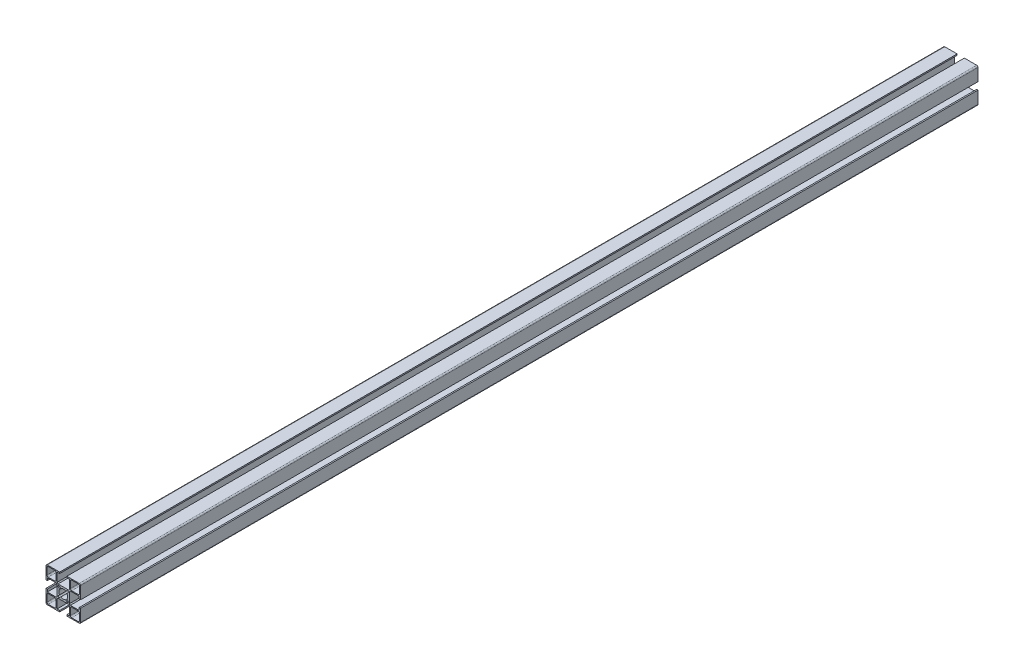
SolidWorks part; units mm, degrees
note: '?' marks a value the reader was unsure of.
material "6063-T5"
ref_plane "前视基准面" through (0, 0, 0) normal (0, 0, 1) x (1, 0, 0)
ref_plane "上视基准面" through (0, 0, 0) normal (0, 1, 0) x (1, 0, 0)
ref_plane "右视基准面" through (0, 0, 0) normal (1, 0, 0) x (0, 0, -1)
sketch "草图1" plane through (0, 0, 0) normal (0, 0, 1) x (1, 0, 0)
  line L0 (-6.0893, -7.15) -> (6.0893, -7.15)
  line L1 (7.15, -8.2107) -> (6.0893, -7.15)
  line L2 (-7.15, -8.2107) -> (-6.0893, -7.15)
  line L3 (7.15, -8.2107) -> (7.15, -18.5)
  line L4 (-7.15, -8.2107) -> (-7.15, -18.5)
  line L5 (4.2, -18.5) -> (7.15, -18.5)
  line L6 (-4.2, -18.5) -> (-7.15, -18.5)
  line L7 (4.2, -18.5) -> (4.2, -20)
  line L8 (-4.2, -18.5) -> (-4.2, -20)
  line L9 (4.2, -20) -> (18.5, -20)
  line L10 (-4.2, -20) -> (-18.5, -20)
  line L11 (20, -18.5) -> (20, -4.2)
  line L12 (-20, -18.5) -> (-20, -4.2)
  line L13 (20, -4.2) -> (18.5, -4.2)
  line L14 (-20, -4.2) -> (-18.5, -4.2)
  line L15 (18.5, -4.2) -> (18.5, -7.15)
  line L16 (-18.5, -4.2) -> (-18.5, -7.15)
  line L17 (18.5, -7.15) -> (8.2107, -7.15)
  line L18 (-18.5, -7.15) -> (-8.2107, -7.15)
  line L19 (8.2107, -7.15) -> (7.15, -6.0893)
  line L20 (-8.2107, -7.15) -> (-7.15, -6.0893)
  line L21 (7.15, 6.0893) -> (7.15, -6.0893)
  line L22 (-7.15, 6.0893) -> (-7.15, -6.0893)
  line L23 (8.2107, 7.15) -> (7.15, 6.0893)
  line L24 (-8.2107, 7.15) -> (-7.15, 6.0893)
  line L25 (18.5, 7.15) -> (8.2107, 7.15)
  line L26 (-18.5, 7.15) -> (-8.2107, 7.15)
  line L27 (18.5, 4.2) -> (18.5, 7.15)
  line L28 (-18.5, 4.2) -> (-18.5, 7.15)
  line L29 (20, 4.2) -> (18.5, 4.2)
  line L30 (-20, 4.2) -> (-18.5, 4.2)
  line L31 (20, 18.5) -> (20, 4.2)
  line L32 (-20, 18.5) -> (-20, 4.2)
  line L33 (4.2, 20) -> (18.5, 20)
  line L34 (-4.2, 20) -> (-18.5, 20)
  line L35 (4.2, 18.5) -> (4.2, 20)
  line L36 (-4.2, 18.5) -> (-4.2, 20)
  line L37 (4.2, 18.5) -> (7.15, 18.5)
  line L38 (-4.2, 18.5) -> (-7.15, 18.5)
  line L39 (7.15, 8.2107) -> (7.15, 18.5)
  line L40 (-7.15, 8.2107) -> (-7.15, 18.5)
  line L41 (7.15, 8.2107) -> (6.0893, 7.15)
  line L42 (-7.15, 8.2107) -> (-6.0893, 7.15)
  line L43 (6.0893, 7.15) -> (-6.0893, 7.15)
  line L44 (17.4, 8.25) -> (9.75, 8.25)
  line L45 (8.25, 9.75) -> (8.25, 17.4)
  line L46 (18.9, 17.4) -> (18.9, 9.75)
  line L47 (9.75, 18.9) -> (17.4, 18.9)
  line L48 (-8.25, 17.4) -> (-8.25, 9.75)
  line L49 (-17.4, 18.9) -> (-9.75, 18.9)
  line L50 (-9.75, 8.25) -> (-17.4, 8.25)
  line L51 (-18.9, 9.75) -> (-18.9, 17.4)
  line L52 (-17.4, -8.25) -> (-9.75, -8.25)
  line L53 (-8.25, -9.75) -> (-8.25, -17.4)
  line L54 (-18.9, -17.4) -> (-18.9, -9.75)
  line L55 (-9.75, -18.9) -> (-17.4, -18.9)
  line L56 (8.25, -17.4) -> (8.25, -9.75)
  line L57 (17.4, -18.9) -> (9.75, -18.9)
  line L58 (9.75, -8.25) -> (17.4, -8.25)
  line L59 (18.9, -9.75) -> (18.9, -17.4)
  line L60 (-4.2433, 2.8291) -> (-5.6569, 4.2426)
  line L61 (-5.6569, -4.2426) -> (-4.2433, -2.8291)
  line L62 (-4.2426, 5.6569) -> (-2.8291, 4.2433)
  line L63 (-2.8291, -4.2433) -> (-4.2426, -5.6569)
  line L64 (2.8291, 4.2433) -> (4.2426, 5.6569)
  line L65 (4.2426, -5.6569) -> (2.8291, -4.2433)
  line L66 (5.6569, 4.2426) -> (4.2433, 2.8291)
  line L67 (4.2433, -2.8291) -> (5.6569, -4.2426)
  arc A0 (18.5, -20) -> (20, -18.5) centre (18.5, -18.5) ccw
  arc A1 (-20, -18.5) -> (-18.5, -20) centre (-18.5, -18.5) ccw
  arc A2 (20, 18.5) -> (18.5, 20) centre (18.5, 18.5) ccw
  arc A3 (-18.5, 20) -> (-20, 18.5) centre (-18.5, 18.5) ccw
  arc A4 (8.25, 9.75) -> (9.75, 8.25) centre (9.75, 9.75) ccw
  arc A5 (17.4, 8.25) -> (18.9, 9.75) centre (17.4, 9.75) ccw
  arc A6 (9.75, 18.9) -> (8.25, 17.4) centre (9.75, 17.4) ccw
  arc A7 (18.9, 17.4) -> (17.4, 18.9) centre (17.4, 17.4) ccw
  arc A8 (-8.25, 17.4) -> (-9.75, 18.9) centre (-9.75, 17.4) ccw
  arc A9 (-9.75, 8.25) -> (-8.25, 9.75) centre (-9.75, 9.75) ccw
  arc A10 (-17.4, 18.9) -> (-18.9, 17.4) centre (-17.4, 17.4) ccw
  arc A11 (-18.9, 9.75) -> (-17.4, 8.25) centre (-17.4, 9.75) ccw
  arc A12 (-8.25, -9.75) -> (-9.75, -8.25) centre (-9.75, -9.75) ccw
  arc A13 (-17.4, -8.25) -> (-18.9, -9.75) centre (-17.4, -9.75) ccw
  arc A14 (-9.75, -18.9) -> (-8.25, -17.4) centre (-9.75, -17.4) ccw
  arc A15 (-18.9, -17.4) -> (-17.4, -18.9) centre (-17.4, -17.4) ccw
  arc A16 (8.25, -17.4) -> (9.75, -18.9) centre (9.75, -17.4) ccw
  arc A17 (9.75, -8.25) -> (8.25, -9.75) centre (9.75, -9.75) ccw
  arc A18 (17.4, -18.9) -> (18.9, -17.4) centre (17.4, -17.4) ccw
  arc A19 (18.9, -9.75) -> (17.4, -8.25) centre (17.4, -9.75) ccw
  arc A20 (-4.2433, 2.8291) -> (-4.2433, -2.8291) centre (0, 0) ccw
  arc A21 (-4.2426, 5.6569) -> (-5.6569, 4.2426) centre (-4.9497, 4.9497) ccw
  arc A22 (-5.6569, -4.2426) -> (-4.2426, -5.6569) centre (-4.9497, -4.9497) ccw
  arc A23 (2.8291, 4.2433) -> (-2.8291, 4.2433) centre (0, 0) ccw
  arc A24 (-2.8291, -4.2433) -> (2.8291, -4.2433) centre (0, 0) ccw
  arc A25 (5.6569, 4.2426) -> (4.2426, 5.6569) centre (4.9497, 4.9497) ccw
  arc A26 (4.2426, -5.6569) -> (5.6569, -4.2426) centre (4.9497, -4.9497) ccw
  arc A27 (4.2433, -2.8291) -> (4.2433, 2.8291) centre (0, 0) ccw
extrude "凸台-拉伸1" add sketch "草图1" along normal blind 1040
ref_axis "基准轴" through (0, 0, 0) along (0, 0, 1)?
ref_plane "基准面" through (0, 0, 20) normal (0, 0, -1) x (-1, 0, 0)
hole_wizard "螺纹孔E" [suppressed] positions "草图3" profile "草图2" tap size "M12" standard "GB"
sketch "草图3" plane through (0, 0, 300) normal (0, 0, 1) x (1, 0, 0)
  point P0 (0, 0)
sketch "草图2" plane through (0, 0, 300) normal (1, 0, 0) x (0, -1, 0)
  line L0 (0, 0) -> (0, 31.8174)
  line L1 (0, 31.8174) -> (5.105, 28.75)
  line L2 (5.105, 28.75) -> (5.105, 0)
  line L5 (5.105, 0) -> (0, 0)
  line L10 (0, 31.8174) -> (-5.105, 28.75) construction
  line L11 (0, -6.35) -> (0, 107.95) construction
  dimension "螺纹孔钻头直径" = 10.21
  dimension "螺纹孔钻头深度" = 28.75
  dimension "导头角度" = 118
cosmetic thread "孔螺蚊线1" [suppressed] parameters "D1"=20, "D2"=12
hole_wizard "螺纹孔S" [suppressed] positions "草图5" profile "草图4" tap size "M12" standard "GB"
sketch "草图5" plane through (0, 0, 0) normal (0, 0, -1) x (-1, 0, 0)
  point P0 (0, 0)
sketch "草图4" plane through (0, 0, 0) normal (1, 0, 0) x (0, 1, 0)
  line L0 (0, 0) -> (0, 31.8174)
  line L1 (0, 31.8174) -> (5.105, 28.75)
  line L2 (5.105, 28.75) -> (5.105, 0)
  line L5 (5.105, 0) -> (0, 0)
  line L10 (0, 31.8174) -> (-5.105, 28.75) construction
  line L11 (0, -6.35) -> (0, 107.95) construction
  dimension "螺纹孔钻头直径" = 10.21
  dimension "螺纹孔钻头深度" = 28.75
  dimension "导头角度" = 118
cosmetic thread "孔螺蚊线2" [suppressed] parameters "D1"=20, "D2"=12
other "内孔SA1" [suppressed] parameters "D1"=16.8
sketch "草图6" plane through (0, 20, 0) normal (0, 1, 0) x (1, 0, 0)
  line L0 (-4.2, 0) -> (-18.5, 0) construction
  line L1 (0, -22) -> (0, 22) construction
  circle A0 centre (0, -19) radius 10
  dimension "D1" = 20
  dimension "D2" = 19
other "内孔EA1" [suppressed] parameters "D1"=16.8
sketch "草图7" plane through (0, 20, 0) normal (0, 1, 0) x (1, 0, 0)
  line L0 (-4.2, -300) -> (-18.5, -300) construction
  line L1 (0, -22) -> (0, 22) construction
  circle A0 centre (0, -281) radius 10
  dimension "D1" = 20
  dimension "D2" = 19
other "内孔SB1" [suppressed] parameters "D1"=16.8
sketch "草图8" plane through (-20, 0, 0) normal (-1, 0, 0) x (0, 0, 1)
  line L0 (0, -4.2) -> (0, -18.5) construction
  line L1 (22, 0) -> (-22, 0) construction
  circle A0 centre (19, 0) radius 10
  dimension "D1" = 20
  dimension "D2" = 19
other "内孔EB1" [suppressed] parameters "D1"=16.8
sketch "草图9" plane through (-20, 0, 0) normal (-1, 0, 0) x (0, 0, 1)
  line L0 (300, -4.2) -> (300, -18.5) construction
  line L1 (22, 0) -> (-22, 0) construction
  circle A0 centre (281, 0) radius 10
  dimension "D1" = 20
  dimension "D2" = 19
other "内孔SC1" [suppressed] parameters "D1"=16.8
sketch "草图10" plane through (0, -20, 0) normal (0, -1, 0) x (-1, 0, 0)
  line L0 (-4.2, 0) -> (-18.5, 0) construction
  line L1 (0, 22) -> (0, -22) construction
  circle A0 centre (0, -19) radius 10
  dimension "D1" = 20
  dimension "D2" = 19
other "内孔EC1" [suppressed] parameters "D1"=16.8
sketch "草图11" plane through (0, -20, 0) normal (0, -1, 0) x (-1, 0, 0)
  line L0 (-4.2, -300) -> (-18.5, -300) construction
  line L1 (0, 22) -> (0, -22) construction
  circle A0 centre (0, -281) radius 10
  dimension "D1" = 20
  dimension "D2" = 19
other "内孔SD1" [suppressed] parameters "D1"=16.8
sketch "草图12" plane through (20, 0, 0) normal (1, 0, 0) x (0, 0, -1)
  line L0 (0, 4.2) -> (0, 18.5) construction
  line L1 (22, 0) -> (-22, 0) construction
  circle A0 centre (-19, 0) radius 10
  dimension "D1" = 20
  dimension "D2" = 19
other "内孔ED1" [suppressed] parameters "D1"=16.8
sketch "草图13" plane through (20, 0, 0) normal (1, 0, 0) x (0, 0, -1)
  line L0 (-300, 4.2) -> (-300, 18.5) construction
  line L1 (22, 0) -> (-22, 0) construction
  circle A0 centre (-281, 0) radius 10
  dimension "D1" = 20
  dimension "D2" = 19
other "锚孔SA1" [suppressed] parameters "D1"=40
sketch "草图14" plane through (0, 20, 0) normal (0, 1, 0) x (1, 0, 0)
  line L0 (-4.2, 0) -> (-18.5, 0) construction
  line L1 (0, -22) -> (0, 22) construction
  circle A0 centre (0, -30.2) radius 8.5
  dimension "D1" = 17
  dimension "D2" = 30.2
other "锚孔EA1" [suppressed] parameters "D1"=40
sketch "草图15" plane through (0, 20, 0) normal (0, 1, 0) x (1, 0, 0)
  line L0 (-4.2, -300) -> (-18.5, -300) construction
  line L1 (0, -22) -> (0, 22) construction
  circle A0 centre (0, -269.8) radius 8.5
  dimension "D1" = 17
  dimension "D2" = 30.2
other "锚孔SB1" [suppressed] parameters "D1"=40
sketch "草图16" plane through (-20, 0, 0) normal (-1, 0, 0) x (0, 0, 1)
  line L0 (0, -4.2) -> (0, -18.5) construction
  line L1 (22, 0) -> (-22, 0) construction
  circle A0 centre (30.2, 0) radius 8.5
  dimension "D1" = 17
  dimension "D2" = 30.2
other "锚孔EB1" [suppressed] parameters "D1"=40
sketch "草图17" plane through (-20, 0, 0) normal (-1, 0, 0) x (0, 0, 1)
  line L0 (300, -4.2) -> (300, -18.5) construction
  line L1 (22, 0) -> (-22, 0) construction
  circle A0 centre (269.8, 0) radius 8.5
  dimension "D1" = 17
  dimension "D2" = 30.2
other "锚孔SC1" [suppressed] parameters "D1"=40.1
sketch "草图18" plane through (0, -20, 0) normal (0, -1, 0) x (-1, 0, 0)
  line L0 (-4.2, 0) -> (-18.5, 0) construction
  line L1 (0, 22) -> (0, -22) construction
  circle A0 centre (0, -30.2) radius 8.5
  dimension "D1" = 17
  dimension "D2" = 30.2
other "锚孔EC1" [suppressed] parameters "D1"=40.1
sketch "草图19" plane through (0, -20, 0) normal (0, -1, 0) x (-1, 0, 0)
  line L0 (-4.2, -300) -> (-18.5, -300) construction
  line L1 (0, 22) -> (0, -22) construction
  circle A0 centre (0, -269.8) radius 8.5
  dimension "D1" = 17
  dimension "D2" = 30.2
other "锚孔SD1" [suppressed] parameters "D1"=40.1
sketch "草图20" plane through (20, 0, 0) normal (1, 0, 0) x (0, 0, -1)
  line L0 (0, 4.2) -> (0, 18.5) construction
  line L1 (22, 0) -> (-22, 0) construction
  circle A0 centre (-30.2, 0) radius 8.5
  dimension "D1" = 17
  dimension "D2" = 30.2
other "锚孔ED1" [suppressed] parameters "D1"=40.1
sketch "草图21" plane through (20, 0, 0) normal (1, 0, 0) x (0, 0, -1)
  line L0 (-300, 4.2) -> (-300, 18.5) construction
  line L1 (22, 0) -> (-22, 0) construction
  circle A0 centre (-269.8, 0) radius 8.5
  dimension "D1" = 17
  dimension "D2" = 30.2
